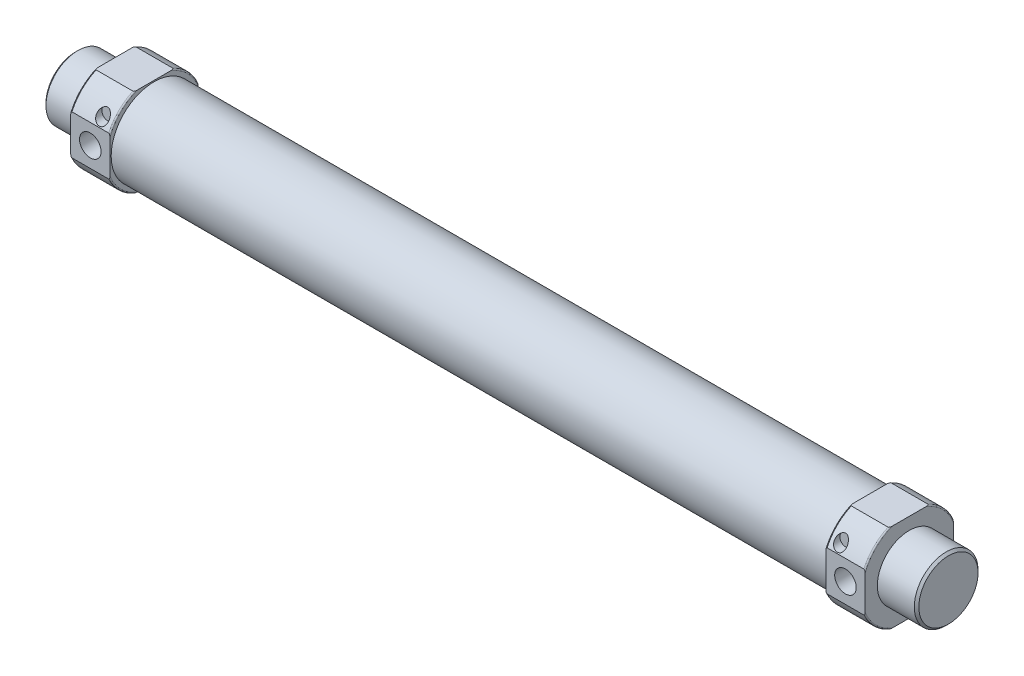
SolidWorks part; units mm, degrees
ref_plane "前视基准面" through (0, 0, 0) normal (0, 0, 1) x (1, 0, 0)
ref_plane "上视基准面" through (0, 0, 0) normal (0, 1, 0) x (1, 0, 0)
ref_plane "右视基准面" through (0, 0, 0) normal (1, 0, 0) x (0, 0, -1)
sketch "草图1" plane through (0, 0, 0) normal (0, 0, 1) x (1, 0, 0)
  line L0 (-32, 0) -> (-32, 12.08)
  line L1 (-32, 12.08) -> (-31.08, 13)
  line L2 (-31.08, 13) -> (-16, 13)
  line L3 (-16, 13) -> (-16, 19.25)
  line L4 (-15.5, 19.75) -> (-0.5, 19.75)
  line L5 (0, 19.25) -> (0, 17.5)
  line L6 (0, 17.5) -> (292, 17.5)
  line L7 (292, 17.5) -> (292, 16.7071)
  line L8 (292, 16.7071) -> (291.2929, 16)
  line L9 (291.2929, 16) -> (10, 16)
  line L10 (10, 16) -> (10, 8.5)
  line L11 (10, 8.5) -> (-18, 8.5)
  line L12 (-18, 8.5) -> (-22.9075, 0)
  line L13 (-22.9075, 0) -> (-32, 0)
  line L14 (10, 0) -> (-32, 0) construction
  arc A0 (-16, 19.25) -> (-15.5, 19.75) centre (-15.5, 19.25) cw
  arc A1 (-0.5, 19.75) -> (0, 19.25) centre (-0.5, 19.25) cw
revolve "旋转1" add sketch "草图1" angle 360 about L14 reverse direction yes
cosmetic thread "装饰螺纹线1" parameters "D1"=16, "D2"=24.16
sketch "草图2" plane through (0, 0, 0) normal (0, 0, 1) x (1, 0, 0)
  line L0 (314.9075, 0) -> (310, 8.5)
  line L1 (310, 8.5) -> (282, 8.5)
  line L2 (282, 8.5) -> (282, 16)
  line L3 (282, 16) -> (292, 16)
  line L4 (292, 16) -> (292, 19.25)
  line L5 (292.5, 19.75) -> (307.5, 19.75)
  line L6 (308, 19.25) -> (308, 13)
  line L7 (308, 13) -> (323.08, 13)
  line L8 (323.08, 13) -> (324, 12.08)
  line L9 (324, 12.08) -> (324, 0)
  line L10 (324, 0) -> (314.9075, 0)
  line L11 (324, 0) -> (282, 0) construction
  arc A0 (292, 19.25) -> (292.5, 19.75) centre (292.5, 19.25) cw
  arc A1 (307.5, 19.75) -> (308, 19.25) centre (307.5, 19.25) cw
revolve "旋转2" add sketch "草图2" angle 360 about L11 reverse direction yes
cosmetic thread "装饰螺纹线2" parameters "D1"=16, "D2"=24.16
ref_plane "基准面1" through (-16, 0, 0) normal (1, 0, 0) x (0, 0, -1)
sketch "草图3" plane through (-16, 0, 0) normal (1, 0, 0) x (0, 0, -1)
  line L0 (-39.5, -39.5) -> (39.5, -39.5)
  line L1 (39.5, -39.5) -> (39.5, 39.5)
  line L2 (39.5, 39.5) -> (-39.5, 39.5)
  line L3 (-39.5, 39.5) -> (-39.5, -39.5)
  line L4 (-18, 18) -> (-18, -18)
  line L5 (-18, -18) -> (18, -18)
  line L6 (18, -18) -> (18, 18)
  line L7 (18, 18) -> (-18, 18)
extrude "切除-拉伸1" cut sketch "草图3" along normal blind 324
ref_plane "基准面2" through (-4.5, 0, 0) normal (1, 0, 0) x (0, 0, -1)
sketch "草图8" plane through (-4.5, 0, 0) normal (1, 0, 0) x (0, 0, -1)
  line L0 (-18, 11) -> (-18, 13.5)
  line L1 (-18, 13.5) -> (-14.3, 13.5)
  line L2 (-14.3, 13.5) -> (-14.3, 11)
  line L3 (-14.3, 11) -> (-18, 11)
  line L4 (-14.3, 11) -> (-18, 11) construction
revolve "切除-旋转1" cut sketch "草图8" angle 360 about L4 reverse direction yes
ref_plane "基准面3" through (296.5, 0, 0) normal (1, 0, 0) x (0, 0, -1)
sketch "草图9" plane through (296.5, 0, 0) normal (1, 0, 0) x (0, 0, -1)
  line L0 (-18, 11) -> (-18, 13.5)
  line L1 (-18, 13.5) -> (-14.3, 13.5)
  line L2 (-14.3, 13.5) -> (-14.3, 11)
  line L3 (-14.3, 11) -> (-18, 11)
  line L4 (-14.3, 11) -> (-18, 11) construction
revolve "切除-旋转2" cut sketch "草图9" angle 360 about L4 reverse direction yes
ref_plane "基准面4" through (-16, 0, 0) normal (1, 0, 0) x (0, 0, -1)
ref_plane "基准面5" through (308, 0, 0) normal (1, 0, 0) x (0, 0, -1)
ref_plane "For Body XY" through (0, 0, 0) normal (-1, 0, 0) x (0, 0, 1)
ref_plane "For Body XZ" through (0, 0, 0) normal (0, 1, 0) x (1, 0, 0)
ref_plane "For Body YZ" through (0, 0, 0) normal (0, 0, -1) x (-1, 0, 0)
ref_axis "For Body X" through (0, 0, 80.9) along (0, 0, -1)
ref_axis "For Body Y" through (0, 50, 0) along (0, -1, 0)
ref_axis "For Body Z" through (-80.9, 0, 0) along (1, 0, 0)
sketch3d "For Body"
  point P0 (0, 0, 0)
ref_plane "For_Nut XY" through (-16, 0, 0) normal (-1, 0, 0) x (0, 0, 1)
ref_plane "For_Nut XZ" through (0, 0, 0) normal (0, 1, 0) x (1, 0, 0)
ref_plane "For_Nut YZ" through (0, 0, 0) normal (0, 0, -1) x (-1, 0, 0)
ref_axis "For_Nut X" through (-16, 0, 80.9) along (0, 0, -1)
ref_axis "For_Nut Y" through (-16, 50, 0) along (0, -1, 0)
ref_axis "For_Nut Z" through (-80.9, 0, 0) along (1, 0, 0)
sketch3d "For_Nut"
  point P0 (-16, 0, 0)
ref_plane "Fou_dummy XY" through (0, 0, 0) normal (1, 0, 0) x (0, 0, -1)
ref_plane "Fou_dummy XZ" through (0, 0, 0) normal (0, -1, 0) x (-1, 0, 0)
ref_plane "Fou_dummy YZ" through (0, 0, 0) normal (0, 0, -1) x (-1, 0, 0)
ref_axis "Fou_dummy X" through (0, 0, 80.9) along (0, 0, -1)
ref_axis "Fou_dummy Y" through (0, -50, 0) along (0, 1, 0)
ref_axis "Fou_dummy Z" through (80.9, 0, 0) along (-1, 0, 0)
sketch3d "Fou_dummy"
  point P0 (0, 0, 0)
ref_plane "for nut2 XY" through (308, 0, 0) normal (1, 0, 0) x (0, 0, -1)
ref_plane "for nut2 XZ" through (0, 0, 0) normal (0, -1, 0) x (-1, 0, 0)
ref_plane "for nut2 YZ" through (0, 0, 0) normal (0, 0, -1) x (-1, 0, 0)
ref_axis "for nut2 X" through (308, 0, 80.9) along (0, 0, -1)
ref_axis "for nut2 Y" through (308, -50, 0) along (0, 1, 0)
ref_axis "for nut2 Z" through (80.9, 0, 0) along (-1, 0, 0)
sketch3d "for nut2"
  point P0 (308, 0, 0)
hole_wizard "G1/8 螺纹孔1" positions "草图11" profile "草图10" tap size "G1/8" standard "ISO" end condition up to next
sketch "草图11" plane through (0, 0, 18) normal (0, 0, 1) x (1, 0, 0)
  line L0 (0, 0) -> (-8, 0) construction
  line L1 (292, 0) -> (300, 0) construction
  line L2 (292, 17.5) -> (292, -17.5) construction
  point P2 (-8, 0)
  point P12 (300, 0)
  dimension "D1" = 8
  dimension "D2" = 8
sketch "草图10" plane through (-8, 0, 18) normal (1, 0, 0) x (0, -1, 0)
  line L0 (0, 0) -> (0, 9.5)
  line L1 (0, 9.5) -> (4.4, 9.5)
  line L2 (4.4, 9.5) -> (4.4, 0)
  line L5 (4.4, 0) -> (0, 0)
  line L11 (0, -6.35) -> (0, 107.95) construction
  dimension "通孔螺纹孔钻头直径" = 8.8
  dimension "通孔螺纹孔钻头深度" = 9.5
cosmetic thread "孔螺蚊线1" parameters "D2"=9.728
cosmetic thread "孔螺蚊线2" parameters "D2"=9.728
